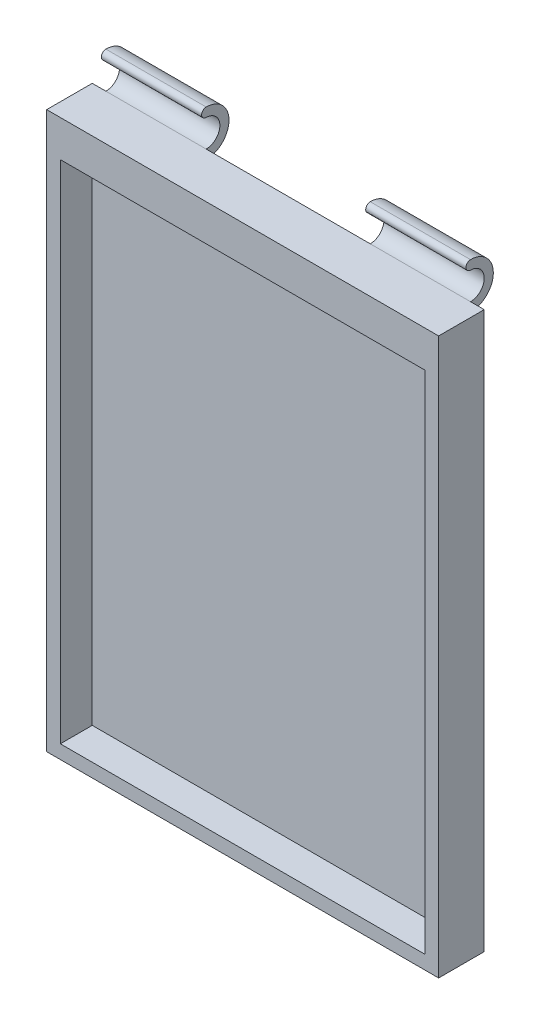
SolidWorks part; units mm, degrees
ref_plane "Ön Düzlem" through (0, 0, 0) normal (0, 0, 1) x (1, 0, 0)
ref_plane "Üst Düzlem" through (0, 0, 0) normal (0, 1, 0) x (1, 0, 0)
ref_plane "Sağ Düzlem" through (0, 0, 0) normal (1, 0, 0) x (0, 0, -1)
sketch "ekran_taban" plane through (0, 0, 0) normal (0, 0, 1) x (1, 0, 0)
  line L0 (-40.0462, 77.6026) -> (45.9538, 77.6026)
  line L1 (-37.0462, 74.6026) -> (42.9538, 74.6026)
  line L2 (-37.0462, 74.6026) -> (-37.0462, -36.3974)
  line L3 (-37.0462, -36.3974) -> (42.9538, -36.3974)
  line L4 (42.9538, 74.6026) -> (42.9538, -36.3974)
  line L5 (45.9538, 77.6026) -> (45.9538, -39.3974)
  line L6 (-40.0462, -39.3974) -> (45.9538, -39.3974)
  line L7 (-40.0462, 77.6026) -> (-40.0462, -39.3974)
extrude "Yükseklik-Ekstrüzyon1" add sketch "ekran_taban" along normal blind 10
extrude "Yükseklik-Ekstrüzyon2" add sketch "ekran_taban<2>" along normal blind 3 contours L4 L1 L2 L3 region at (2.9538, 19.1026, 0)
sketch "ekran_taban<2>" plane through (0, 0, 0) normal (0, 0, 1) x (1, 0, 0) same geometry as "ekran_taban"
sketch "Çizim3" plane through (45.9538, 0, 0) normal (1, 0, 0) x (0, 0, -1)
  line L1 (-10, 77.6026) -> (0, 77.6026)
  line L2 (0, 80.6026) -> (0, 77.6026)
  line L7 (0, 82.6026) -> (-10, 82.6026)
  line L8 (-10, 82.6026) -> (-10, 77.6026)
  arc A0 (0, 90.6026) -> (0, 80.6026) centre (0, 85.6026) cw
  arc A1 (0, 88.6026) -> (0, 82.6026) centre (0, 85.6026) cw
  arc A2 (0, 88.6026) -> (0, 90.6026) centre (0, 89.6026) cw
extrude "Yükseklik-Ekstrüzyon3" add sketch "Çizim3" against normal up to surface (86 mm away) up to face at (-40.0462, 19.1026, 5)
sketch "Çizim6" plane through (0, 82.6026, 0) normal (0, 1, 0) x (1, 0, 0)
  line L8 (45.9538, 5) -> (-40.0462, 5) construction
  line L9 (-40.0462, -10) -> (-37.0462, -10)
  line L10 (-40.0462, -10) -> (-40.0462, 5)
  line L11 (-40.0462, 5) -> (-37.0462, 5)
  line L12 (-37.0462, -10) -> (-37.0462, 5)
  line L13 (-40.0462, -10) -> (45.9538, -10) construction
  line L14 (-15.0462, -10) -> (20.9538, -10)
  line L15 (-15.0462, -10) -> (-15.0462, 5)
  line L16 (-15.0462, 5) -> (20.9538, 5)
  line L17 (20.9538, -10) -> (20.9538, 5)
  line L19 (45.9538, -10) -> (42.9538, -10)
  line L20 (45.9538, -10) -> (45.9538, 5)
  line L21 (45.9538, 5) -> (42.9538, 5)
  line L22 (42.9538, -10) -> (42.9538, 5)
extrude "Kes-Ekstrüzyon3" cut sketch "Çizim6" along normal blind 10
sketch "Çizim8" plane through (0, 82.6026, 0) normal (0, 1, 0) x (1, 0, 0)
  line L0 (-37.0462, 0) -> (-37.0462, 5)
  line L1 (-37.0462, 5) -> (-40.0462, 5)
  line L4 (42.9538, 5) -> (42.9538, 0)
  line L5 (20.9538, 0) -> (20.9538, 5)
  line L6 (20.9538, 5) -> (-15.0462, 5)
  line L7 (-15.0462, 5) -> (-15.0462, 0)
  line L8 (-40.0462, 5) -> (-40.0462, 0)
  line L9 (-40.0462, 0) -> (-37.0462, 0)
  line L10 (-15.0462, 0) -> (20.9538, 0)
  line L12 (42.9538, 5) -> (45.9538, 5)
  line L13 (45.9538, 5) -> (45.9538, 0)
  line L14 (45.9538, 0) -> (42.9538, 0)
extrude "Kes-Ekstrüzyon5" cut sketch "Çizim8" against normal blind 2
